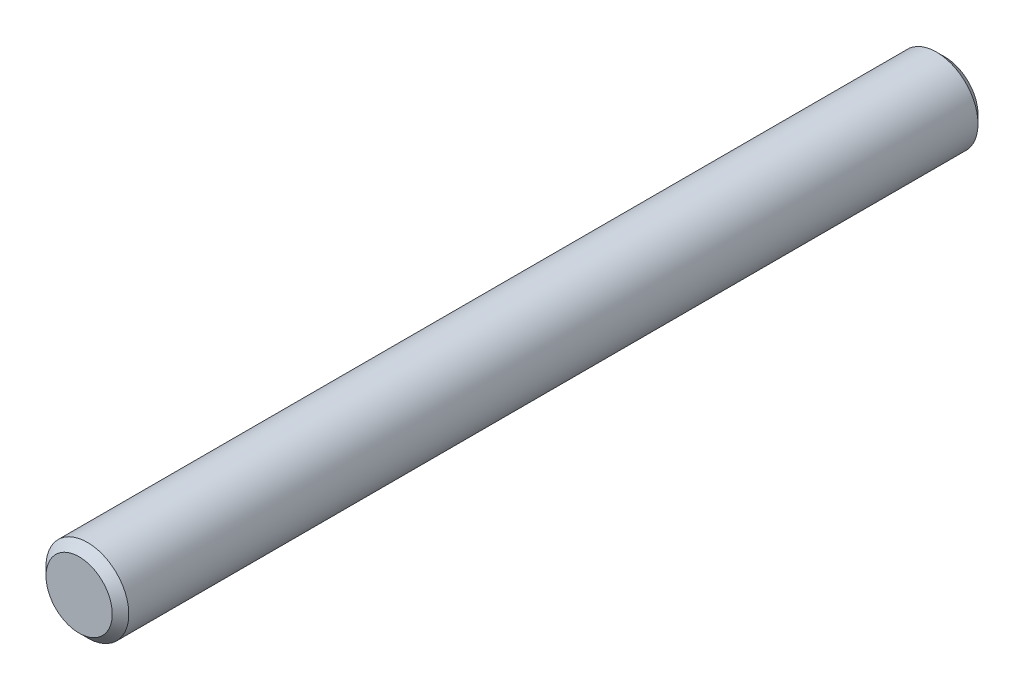
SolidWorks part; units mm, degrees
ref_plane "Front" through (0, 0, 0) normal (0, 0, 1) x (1, 0, 0)
ref_plane "Top" through (0, 0, 0) normal (0, 1, 0) x (1, 0, 0)
ref_plane "Right" through (0, 0, 0) normal (1, 0, 0) x (0, 0, -1)
sketch "Sketch1" plane through (0, 0, 0) normal (0, 0, 1) x (1, 0, 0)
  circle A0 centre (0, 0) radius 4.7625
  dimension "dia" = 9.525
extrude "Extrude1" add sketch "Sketch1" along normal mid plane 99.568
sketch "Sketch2" plane through (0, 0, 0) normal (1, 0, 0) x (0, 0, -1)
  line L0 (49.784, 4.7625) -> (47.244, 4.7625) construction
  line L1 (49.784, 4.7625) -> (-49.784, 4.7625) construction
  line L2 (47.244, 4.7625) -> (42.3088, 4.7625) construction
  line L3 (42.3088, 4.7625) -> (32.3012, 4.7625) construction
  line L4 (32.3012, 4.7625) -> (27.366, 4.7625) construction
  line L8 (37.305, 4.7625) -> (37.305, -4.7625) construction
  line L9 (-49.784, -4.7625) -> (49.784, -4.7625) construction
  line L10 (27.366, 4.7625) -> (17.3584, 4.7625) construction
  line L11 (17.3584, 4.7625) -> (12.4231, 4.7625) construction
  line L12 (12.4231, 4.7625) -> (2.4155, 4.7625) construction
  line L13 (2.4155, 4.7625) -> (-2.5197, 4.7625) construction
  line L14 (-2.5197, 4.7625) -> (-12.5273, 4.7625) construction
  line L15 (24.826, 4.7625) -> (24.826, -4.7625) construction
  line L16 (9.8831, 4.7625) -> (9.8831, -4.7625) construction
  line L17 (-5.0597, 4.7625) -> (-5.0597, -4.7625) construction
  line L18 (-12.5273, 4.7625) -> (-17.4625, 4.7625) construction
  line L19 (34.8412, 4.7625) -> (39.7688, 4.7625) construction
  line L20 (34.8412, 4.7625) -> (34.8412, -4.7625) construction
  line L21 (34.8412, -4.7625) -> (39.7688, -4.7625) construction
  line L22 (39.7688, 4.7625) -> (39.7688, -4.7625) construction
  line L23 (-17.4625, 4.7625) -> (-27.4701, 4.7625) construction
  line L24 (-27.4701, 4.7625) -> (-32.4053, 4.7625) construction
  line L25 (-32.4053, 4.7625) -> (-42.4129, 4.7625) construction
  line L26 (-42.4129, 4.7625) -> (-47.3405, 4.7625) construction
  line L27 (-20.0025, 4.7625) -> (-20.0025, -4.7625) construction
  line L28 (-34.9453, 4.7625) -> (-34.9453, -4.7625) construction
  point P0 (-49.784, 4.7625)
  point P1 (49.784, 4.7625)
  point P30 (37.305, 4.7625)
  dimension "D1" = 2.54
  dimension "D2" = 4.9352
  dimension "D3" = 10.0076
  dimension "D4" = 4.9352
  dimension "D5" = 10.0076
  dimension "D6" = 4.9352
  dimension "D7" = 10.0076
  dimension "D8" = 4.9352
  dimension "D9" = 10.0076
  dimension "D10" = 4.9276
  dimension "D11" = 2.54
  dimension "D12" = 2.54
  dimension "D13" = 2.54
  dimension "D14" = 4.9352
  dimension "D15" = 4.9352
  dimension "D16" = 10.0076
  dimension "D17" = 10.0076
  dimension "D18" = 4.9276
  dimension "D19" = 2.54
  dimension "D20" = 2.54
chamfer "Chamfer1" distance 0.9525 angle 45 2 edges at (4.7625, 0, -49.784) (4.7625, 0, 49.784)
equation "\"D1@Chamfer1\" = \"dia@Sketch1\" * .1"
